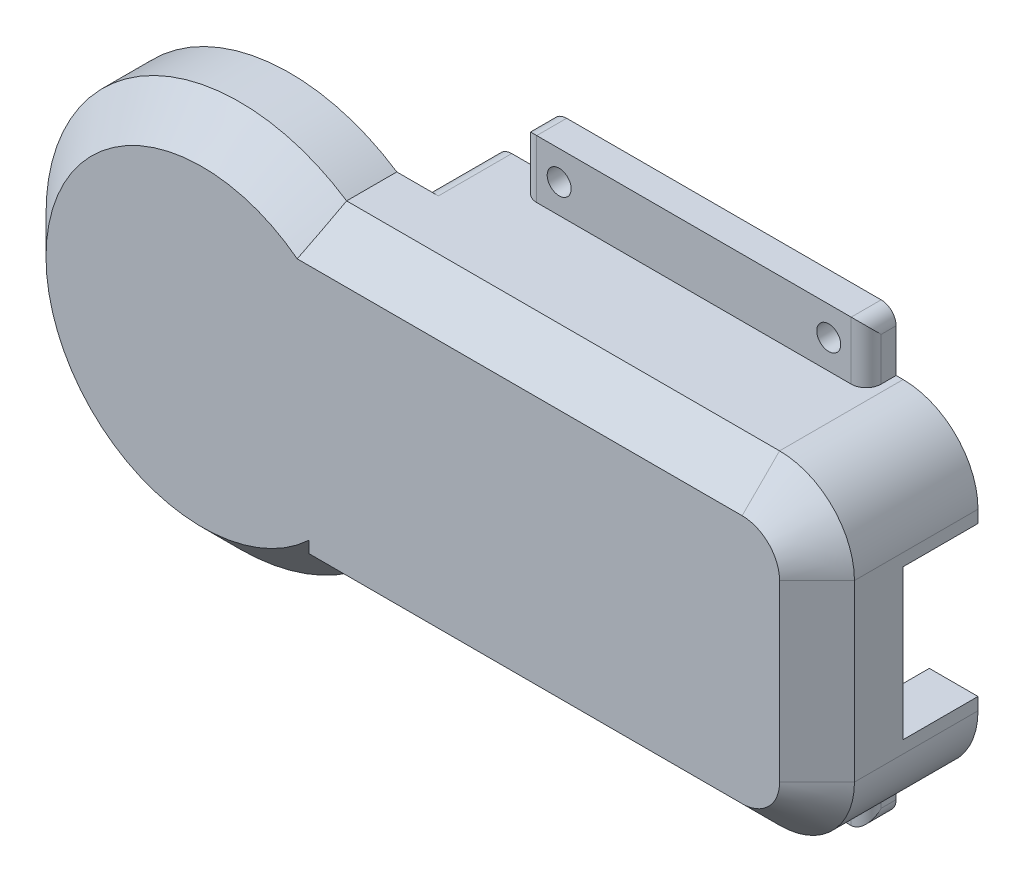
SolidWorks part; units mm, degrees
ref_plane "Alzado" through (0, 0, 0) normal (0, 0, 1) x (1, 0, 0)
ref_plane "Planta" through (0, 0, 0) normal (0, 1, 0) x (1, 0, 0)
ref_plane "Vista lateral" through (0, 0, 0) normal (1, 0, 0) x (0, 0, -1)
sketch "Croquis1" plane through (0, 0, 0) normal (0, 0, 1) x (1, 0, 0)
  line L1 (27.435, 10.11) -> (-27.435, 10.11) construction
  line L2 (27.435, 10.11) -> (27.435, -10.11) construction
  line L3 (27.435, -10.11) -> (-27.435, -10.11) construction
  line L4 (-27.435, 10.11) -> (-27.435, -10.11) construction
  line L5 (27.435, 10.11) -> (-27.435, -10.11) construction
  line L6 (27.435, -10.11) -> (-27.435, 10.11) construction
  line L7 (-33.935, 21.655) -> (33.935, 21.655)
  line L8 (33.935, 21.655) -> (33.935, -21.655)
  line L9 (33.935, -21.655) -> (-33.935, -21.655)
  line L12 (-27.435, -10.11) -> (27.435, -10.11)
  line L13 (27.435, -10.11) -> (27.435, 10.11)
  line L16 (-33.935, 15.155) -> (27.435, 15.155)
  line L17 (27.435, 15.155) -> (27.435, -15.155)
  line L18 (27.435, -15.155) -> (-33.935, -15.155)
  line L19 (-33.935, 21.655) -> (-33.935, 15.155)
  line L20 (-33.935, -15.155) -> (-33.935, -21.655)
  point P0 (0, 0)
  point P13 (33.935, 0)
  dimension "D1" = 54.87
  dimension "D2" = 20.22
  dimension "D3" = 43.31
  dimension "D4" = 6.5
  dimension "D5" = 6.5
  dimension "D6" = 6.5
extrude "Saliente-Extruir1" add sketch "Croquis1" along normal blind 15 contours L18 L20 L9 L8 L7 L19 L16 L17 L13 region at (0, 20.8499, 0)
sketch "Croquis2" plane through (0, 0, 15) normal (0, 0, 1) x (1, 0, 0)
  line L1 (-33.935, 21.655) -> (33.935, 21.655) construction
  line L2 (-33.935, 21.655) -> (33.935, 21.655)
  line L3 (-33.935, 21.655) -> (-33.935, -21.655)
  line L4 (-33.935, -21.655) -> (33.935, -21.655)
  line L5 (33.935, 21.655) -> (33.935, -21.655)
  line L6 (-33.935, 21.655) -> (-33.935, 15.155) construction
extrude "Saliente-Extruir2" add sketch "Croquis2" along normal blind 6.5
sketch "Croquis3" plane through (0, 0, 15) normal (0, 0, -1) x (-1, 0, 0)
  line L0 (27.435, 10.11) -> (27.435, -10.11) construction
  line L2 (-27.435, 10.11) -> (27.435, 10.11) construction
  circle A0 centre (16.135, 0.11) radius 2.6
  dimension "D1" = 5.2
  dimension "D2" = 11.3
  dimension "D3" = 10
fillet "Redondeo3" radius 10 2 edges at (33.935, -21.655, 10.75) (33.935, 21.655, 10.75)
sketch "Croquis4" plane through (0, 0, 0) normal (0, 0, -1) x (-1, 0, 0)
  line L0 (33.935, 21.655) -> (-23.935, 21.655) construction
  line L4 (23, 29.405) -> (23, 21.655)
  line L5 (0, 0) -> (0, 21.655) construction
  line L7 (-23, 29.405) -> (-23, 21.655)
  line L10 (0, 0) -> (-27.435, 0) construction
  line L11 (-27.435, 15.155) -> (-27.435, -15.155) construction
  line L13 (23, -29.405) -> (23, -21.655)
  line L18 (-23, -29.405) -> (-23, -21.655)
  line L20 (-23, -21.655) -> (23, -21.655)
  line L21 (-23, -29.405) -> (23, -29.405)
  line L22 (-23, 29.405) -> (23, 29.405)
  line L23 (-23, 21.655) -> (23, 21.655)
  dimension "D1" = 7.75
  dimension "D2" = 46
extrude "Saliente-Extruir4" add sketch "Croquis4" against normal blind 4
chamfer "Chaflán2" distance 3.5 angle 45 2 edges at (-3.25, -15.155, 0) (-3.25, 15.155, 0)
chamfer "Chaflán1" distance 5 angle 45 5 edges at (-5, -21.655, 21.5) (-5, 21.655, 21.5) (31.0061, -18.7261, 21.5) (33.935, 0, 21.5) (31.0061, 18.7261, 21.5)
sketch "Croquis5" plane through (0, 0, 15) normal (0, 0, -1) x (-1, 0, 0)
  circle A0 centre (16.135, 0.11) radius 12.76 construction
  circle A1 centre (48.18, 0.11) radius 22.285 construction
  circle A2 centre (48.18, 0.11) radius 20.785 construction
  circle A3 centre (16.135, 0.11) radius 11.26 construction
  circle A4 centre (48.18, 0.11) radius 25.855
  dimension "D1" = 25.52
  dimension "D2" = 44.57
  dimension "D3" = 41.57
  dimension "D4" = 22.52
  dimension "D5" = 3.57
extrude "Cortar-Extruir1" cut sketch "Croquis5" along normal up to surface (15 mm away) up to face at (2.1673, 0, 0)
sketch "Croquis6" plane through (0, 0, 21.5) normal (0, 0, 1) x (1, 0, 0)
  circle A0 centre (-48.18, 0.11) radius 25.855 construction
  circle A1 centre (-48.18, 0.11) radius 25.855
extrude "Saliente-Extruir5" add sketch "Croquis6" against normal up to surface (6.5 mm away) up to face at (-14.3963, 3.1222, 15)
sketch "Croquis7" plane through (0, 0, 15) normal (0, 0, -1) x (-1, 0, 0)
  line L0 (48.18, 2.465) -> (48.18, -2.685) construction
  circle A0 centre (48.18, -0.11) radius 2.575
  dimension "D1" = 5.15
  dimension "D2" = 0.22
extrude "Saliente-Extruir6" add sketch "Croquis7" along normal blind 6.7
sketch "Croquis8" plane through (0, 0, 15) normal (0, 0, -1) x (-1, 0, 0)
  line L0 (27.1531, 15.155) -> (27.3123, -15.155) construction
  line L6 (27.1531, 15.155) -> (30.3165, 15.155)
  line L7 (27.3123, -15.155) -> (30.5041, -15.155)
  circle A15 centre (48.18, 0.11) radius 25.855 construction
  arc A16 (27.3123, -15.155) -> (27.1531, 15.155) centre (48.18, 0.11) ccw
  arc A17 (30.5041, -15.155) -> (30.3165, 15.155) centre (48.18, 0.11) ccw
  arc A18 (29.3301, -13.679) -> (29.1863, 13.7003) centre (48.18, 0.11) ccw construction
  dimension "D1" = 2.5
chamfer "Chaflán3" distance 5 angle 45 1 edges at (-74.0346, 0.2538, 21.5)
sketch "Croquis9" plane through (0, 0, 4) normal (0, 0, 1) x (1, 0, 0)
  line L1 (-23, 21.655) -> (-23, 29.405) construction
  line L2 (0, 0) -> (0, 21.655) construction
  line L3 (-33.8869, 21.655) -> (23.935, 21.655) construction
  line L4 (0, 0) -> (33.935, 0) construction
  line L5 (33.935, 11.655) -> (33.935, -11.655) construction
  line L6 (-23, 21.655) -> (-23, 29.405) construction
  circle A0 centre (-18, 25.53) radius 1.6
  circle A1 centre (18, 25.53) radius 1.6
  circle A2 centre (18, -25.53) radius 1.6
  circle A3 centre (-18, -25.53) radius 1.6
  point P8 (-23, 25.53)
  dimension "D1" = 3.2
  dimension "D2" = 5
extrude "Cortar-Extruir2" cut sketch "Croquis9" against normal through all
extrude "Saliente-Extruir9" add sketch "Croquis8" along normal blind 5.2 contours L6 A17 L7 A16
fillet "Redondeo6" radius 2 8 edges at (-23, -25.53, 4) (23, -25.53, 4) (-23, 25.53, 4) (23, 25.53, 4) (23, -29.405, 2) (-23, -29.405, 2) (23, 29.405, 2) (-23, 29.405, 2)
fillet "Redondeo4" radius 2 2 edges at (-33.935, -21.655, 8.25) (-33.8869, 21.655, 4.9)
fillet "Redondeo5" radius 2 1 edges at (-33.3496, -21.0688, 4.9)
sketch "Croquis10" plane through (0, 0, 4) normal (0, 0, 1) x (1, 0, 0)
  circle A0 centre (-18, 25.53) radius 3.66
  dimension "D1" = 7.32
sketch "Croquis11" plane through (27.435, 0, 0) normal (-1, 0, 0) x (0, 0, 1)
  line L0 (0, 18.655) -> (0, -18.655) construction
  line L1 (0, 10) -> (10, 10)
  line L2 (0, 10) -> (0, -10)
  line L3 (0, -10) -> (10, -10)
  line L4 (10, 10) -> (10, -10)
  point P6 (0, 0)
  dimension "D1" = 20
  dimension "D2" = 10
extrude "Cortar-Extruir3" cut sketch "Croquis11" against normal through all
